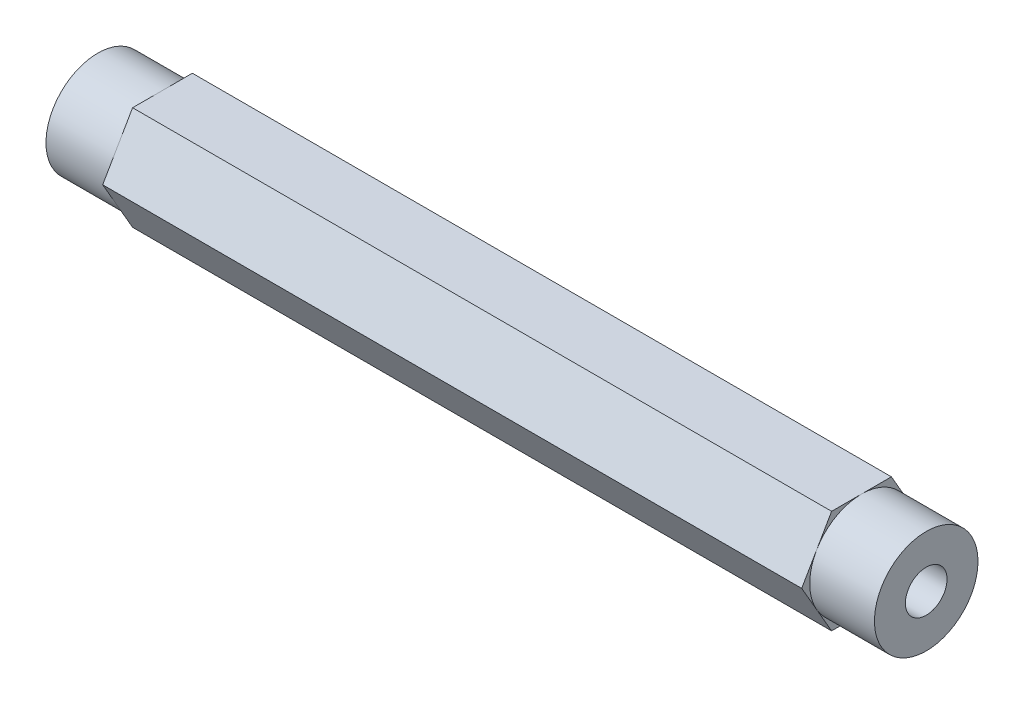
SolidWorks part; units mm, degrees
material "6061-T6 (SS)"
ref_plane "Front Plane" through (0, 0, 0) normal (0, 0, 1) x (1, 0, 0)
ref_plane "Top Plane" through (0, 0, 0) normal (0, 1, 0) x (1, 0, 0)
ref_plane "Right Plane" through (0, 0, 0) normal (1, 0, 0) x (0, 0, -1)
sketch "Sketch2" plane through (0, 0, 0) normal (1, 0, 0) x (0, 0, -1)
  line L1 (7.3323, 0) -> (3.6662, 6.35)
  line L2 (3.6662, 6.35) -> (-3.6662, 6.35)
  line L3 (-3.6662, 6.35) -> (-7.3323, 0)
  line L4 (-7.3323, 0) -> (-3.6662, -6.35)
  line L5 (-3.6662, -6.35) -> (3.6662, -6.35)
  line L6 (3.6662, -6.35) -> (7.3323, 0)
  circle A0 centre (0, 0) radius 6.35 construction
  dimension "D1" = 12.7
extrude "Boss-Extrude1" add sketch "Sketch2" along normal mid plane 101.6
sketch "Sketch3" plane through (50.8, 0, 0) normal (1, 0, 0) x (0, 0, -1)
  circle A0 centre (0, 0) radius 6.35
  dimension "D1" = 12.7
extrude "Cut-Extrude-Thin1" cut sketch "Sketch3" against normal blind 7.9375 thin thin type one direction wall 2.54
mirror "Mirror1" about plane through (0, 0, 0) normal (1, 0, 0) of "Cut-Extrude-Thin1"
hole_wizard "1/4-20 Tapped Hole1" positions "3DSketch1" profile "Sketch5" tap size "1/4-20" standard "ANSI Inch"
sketch3d "3DSketch1"
  line L0 (42.8625, 0, 0) -> (50.8, 0, 0) construction
  line L1 (-42.8625, 0, 0) -> (-50.8, 0, 0) construction
  point P0 (50.8, 0, 0)
  point P4 (-50.8, 0, 0)
sketch "Sketch5" plane through (50.8, 0, 0) normal (0, 1, 0) x (0, 0, -1)
  line L0 (0, 0) -> (0, 18.0438)
  line L1 (0, 18.0438) -> (2.5527, 16.51)
  line L2 (2.5527, 16.51) -> (2.5527, 0)
  line L5 (2.5527, 0) -> (0, 0)
  line L10 (0, 18.0438) -> (-2.5527, 16.51) construction
  line L11 (0, -6.35) -> (0, 107.95) construction
  dimension "Tap Drill Dia." = 5.1054
  dimension "Tap Drill Depth" = 16.51
  dimension "Drill Angle" = 118
cosmetic thread "Hole Thread1" parameters "D1"=12.7, "D2"=6.35
cosmetic thread "Hole Thread2" parameters "D1"=12.7, "D2"=6.35
